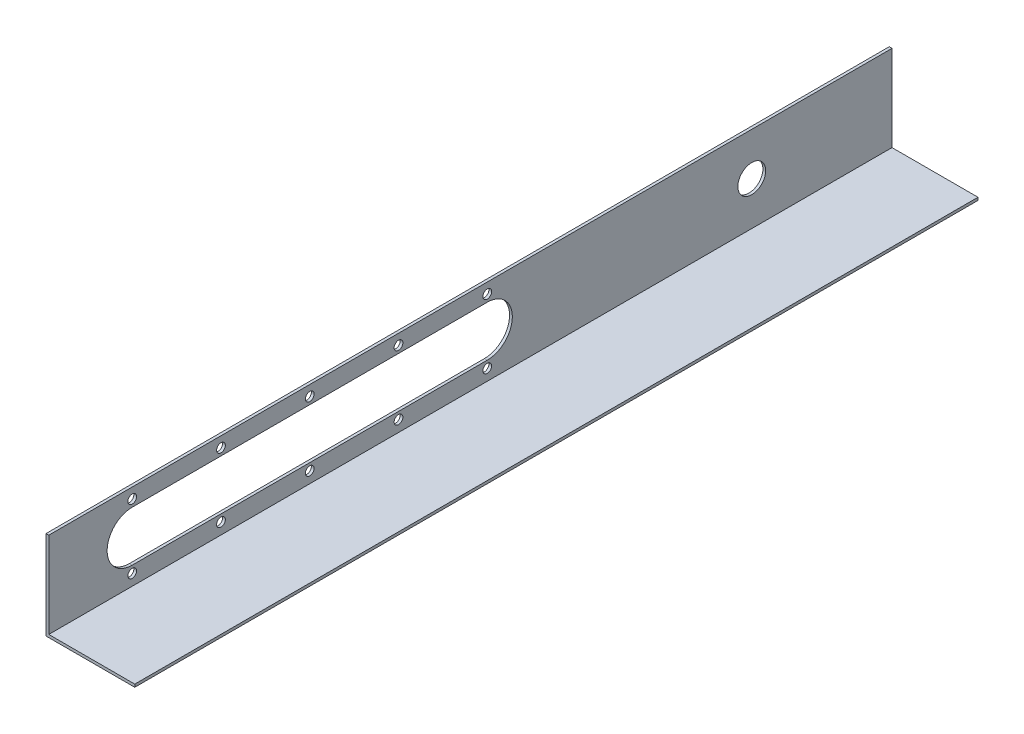
SolidWorks part; units mm, degrees
material "6061 Alloy"
ref_plane "Front Plane" through (0, 0, 0) normal (0, 0, 1) x (1, 0, 0)
ref_plane "Top Plane" through (0, 0, 0) normal (0, 1, 0) x (1, 0, 0)
ref_plane "Right Plane" through (0, 0, 0) normal (1, 0, 0) x (0, 0, -1)
sketch "Sketch3" plane through (0, 0, 0) normal (0, 0, 1) x (1, 0, 0)
  line L0 (0, 0) -> (0, 49.2125)
  line L1 (0, 49.2125) -> (-1.5875, 49.2125)
  line L2 (-1.5875, 49.2125) -> (-1.5875, -1.5875)
  line L3 (-1.5875, -1.5875) -> (49.2125, -1.5875)
  line L4 (49.2125, -1.5875) -> (49.2125, 0)
  line L5 (49.2125, 0) -> (0, 0)
  dimension "D1" = 1.5875
  dimension "D2" = 1.5875
  dimension "D3" = 50.8
  dimension "D4" = 50.8
extrude "Boss-Extrude2" add sketch "Sketch3" along normal blind 482.6
sketch "Sketch6" plane through (0, 0, 0) normal (1, 0, 0) x (0, 0, -1)
  line L0 (-434.848, 24.8285) -> (-231.648, 24.8285) construction
  line L1 (-434.848, 39.1795) -> (-231.648, 39.1795)
  line L2 (-434.848, 10.4775) -> (-231.648, 10.4775)
  line L3 (-482.6, 0) -> (-482.6, 49.2125) construction
  line L5 (-482.6, 49.2125) -> (0, 49.2125) construction
  arc A0 (-434.848, 39.1795) -> (-434.848, 10.4775) centre (-434.848, 24.8285) ccw
  arc A1 (-231.648, 10.4775) -> (-231.648, 39.1795) centre (-231.648, 24.8285) ccw
  point P2 (-333.248, 24.8285)
  dimension "D3" = 47.752
  dimension "D1" = 28.702
  dimension "D2" = 203.2
  dimension "D4" = 24.384
extrude "Cut-Extrude3" cut sketch "Sketch6" against normal through all
sketch "Sketch7" plane through (0, 0, 0) normal (1, 0, 0) x (0, 0, -1)
  line L0 (-482.6, 0) -> (-482.6, 49.2125) construction
  line L1 (-482.6, 49.2125) -> (0, 49.2125) construction
  circle A0 centre (-80.264, 24.7736) radius 7.9629
  dimension "D1" = 15.9258
  dimension "D3" = 24.4389
  dimension "D4" = 402.336
extrude "Cut-Extrude4" cut sketch "Sketch7" against normal through all
sketch "Sketch10" plane through (0, 0, 0) normal (1, 0, 0) x (0, 0, -1)
  line L0 (-434.848, 43.2435) -> (-333.248, 43.2435) construction
  line L1 (-333.248, 43.2435) -> (-231.648, 43.2435) construction
  line L2 (-434.848, 6.4135) -> (-333.248, 6.4135) construction
  line L3 (-333.248, 6.4135) -> (-231.648, 6.4135) construction
  line L6 (-231.648, 43.2435) -> (-434.848, 43.2435)
  line L7 (-231.648, 43.2435) -> (-434.848, 43.2435) construction
  line L9 (-434.848, 6.4135) -> (-231.648, 6.4135)
  line L10 (-434.848, 6.4135) -> (-231.648, 6.4135) construction
  point P1 (-333.248, 6.4135)
  point P6 (-384.048, 43.2435)
  point P7 (-434.848, 6.4135)
  point P8 (-434.848, 43.2435)
  point P9 (-231.648, 43.2435)
  point P10 (-231.648, 6.4135)
  point P13 (-282.448, 43.2435)
  point P14 (-282.448, 6.4135)
  point P15 (-384.048, 6.4135)
  point P17 (-333.248, 6.4135)
  point P21 (-333.248, 43.2435)
  dimension "D1" = 4.064
  dimension "D2" = 4.064
hole_wizard "#10 (0.1935) Diameter Hole1" positions "Sketch11" profile "Sketch12" hole size "#10" standard "ANSI Inch" end condition through all
sketch "Sketch11" plane through (0, 0, 0) normal (1, 0, 0) x (0, 0, -1)
  point P0 (-434.848, 43.2435)
  point P3 (-384.048, 43.2435)
  point P6 (-333.248, 43.2435)
  point P9 (-282.448, 43.2435)
  point P12 (-231.648, 43.2435)
  point P15 (-231.648, 6.4135)
  point P18 (-282.448, 6.4135)
  point P21 (-333.248, 6.4135)
  point P24 (-384.048, 6.4135)
  point P27 (-434.848, 6.4135)
sketch "Sketch12" plane through (0, 43.2435, 434.848) normal (0, 1, 0) x (0, 0, -1)
  line L0 (0, 0) -> (0, 1.5875)
  line L1 (0, 1.5875) -> (2.5, 1.5875)
  line L2 (2.5, 1.5875) -> (2.5, 0)
  line L5 (2.5, 0) -> (0, 0)
  line L11 (0, -6.35) -> (0, 107.95) construction
  dimension "Thru Hole Dia." = 5
  dimension "Thru Hole Depth" = 1.5875
sketch "Sketch13" plane through (0, -1.5875, 0) normal (0, -1, 0) x (1, 0, 0)
  line L0 (23.8125, 469.9) -> (23.8125, 260.35) construction
  line L1 (26.3922, 469.9) -> (26.3922, 260.35)
  line L2 (21.2328, 469.9) -> (21.2328, 260.35)
  line L3 (23.8125, 12.7) -> (23.8125, 222.25) construction
  line L4 (21.2328, 12.7) -> (21.2328, 222.25)
  line L5 (26.3922, 12.7) -> (26.3922, 222.25)
  line L6 (-1.5875, 482.6) -> (49.2125, 482.6) construction
  line L7 (-1.5875, 0) -> (49.2125, 0) construction
  arc A0 (26.3922, 469.9) -> (21.2328, 469.9) centre (23.8125, 469.9) ccw
  arc A1 (21.2328, 260.35) -> (26.3922, 260.35) centre (23.8125, 260.35) ccw
  arc A2 (21.2328, 12.7) -> (26.3922, 12.7) centre (23.8125, 12.7) ccw
  arc A3 (26.3922, 222.25) -> (21.2328, 222.25) centre (23.8125, 222.25) ccw
  point P2 (23.8125, 365.125)
  point P8 (23.8125, 117.475)
  dimension "D1" = 12.7
  dimension "D2" = 209.55
  dimension "D3" = 5.1594
  dimension "D4" = 12.7
